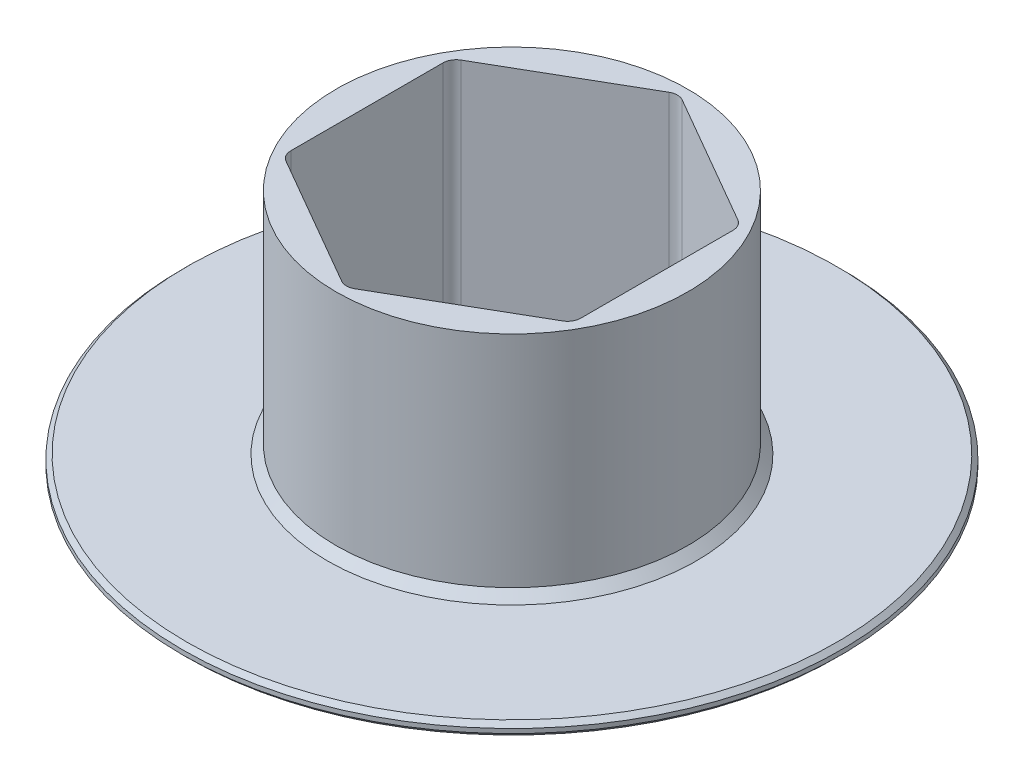
SolidWorks part; units mm, degrees
ref_plane "Front Plane" through (0, 0, 0) normal (0, 0, 1) x (1, 0, 0)
ref_plane "Top Plane" through (0, 0, 0) normal (0, 1, 0) x (1, 0, 0)
ref_plane "Right Plane" through (0, 0, 0) normal (1, 0, 0) x (0, 0, -1)
sketch "Sketch1" plane through (0, 0, 0) normal (0, 1, 0) x (1, 0, 0)
  line L1 (33, -19.0526) -> (33, 19.0526)
  line L2 (33, 19.0526) -> (0, 38.1051)
  line L3 (0, 38.1051) -> (-33, 19.0526)
  line L4 (-33, 19.0526) -> (-33, -19.0526)
  line L5 (-33, -19.0526) -> (0, -38.1051)
  line L6 (0, -38.1051) -> (33, -19.0526)
  circle A0 centre (0, 0) radius 75
  circle A1 centre (0, 0) radius 40
  circle A2 centre (0, 0) radius 33 construction
  dimension "D2" = 80
  dimension "D3" = 150
  dimension "D1" = 66
extrude "Boss-Extrude1" add sketch "Sketch1" along normal blind 3 contours A0 A1 | A1 L6 L5 L4 L3 L2 L1 | L5 L6 L1 L2 L3 L4 region at (0, 0, 0) region at (-72.8787, 0, 0) region at (-38.8686, 0, 0)
extrude "Boss-Extrude2" add sketch "Sketch1<3>" along normal blind 55 contours A1 L6 L5 L4 L3 L2 L1 region at (-38.8686, 0, 0)
sketch "Sketch1<3>" plane through (0, 0, 0) normal (0, 1, 0) x (1, 0, 0) same geometry as "Sketch1"
sketch "Sketch2" plane through (0, 3, 0) normal (0, 1, 0) x (1, 0, 0)
  circle A0 centre (0, 0) radius 26
  dimension "D1" = 52
extrude "Cut-Extrude1" cut sketch "Sketch2" against normal through all
fillet "Fillet1" radius 3 6 edges at (33, 29, 19.0526) (0, 29, 38.1051) (-33, 29, 19.0526) (-33, 29, -19.0526) (0, 29, -38.1051) (33, 29, -19.0526)
chamfer "Chamfer2" distance 2 angle 45 12 edges at (-16.5, 3, -28.5788) (0, 3, -37.641) (-32.5981, 3, -18.8205) (16.5, 3, -28.5788) (-33, 3, 0) (32.5981, 3, -18.8205) (-32.5981, 3, 18.8205) (33, 3, 0) (-16.5, 3, 28.5788) (32.5981, 3, 18.8205) (0, 3, 37.641) (16.5, 3, 28.5788)
chamfer "Chamfer3" distance 2 angle 45 1 edges at (0, 3, 40)
chamfer "Chamfer4" distance 1 angle 45 2 edges at (0, 3, 75) (0, 0, 75)
sketch "Sketch3" plane through (0, 0, 0) normal (0, -1, 0) x (1, 0, 0)
  line L1 (32.5, -18.7639) -> (32.5, 18.7639)
  line L2 (32.5, 18.7639) -> (0, 37.5278)
  line L3 (0, 37.5278) -> (-32.5, 18.7639)
  line L4 (-32.5, 18.7639) -> (-32.5, -18.7639)
  line L5 (-32.5, -18.7639) -> (0, -37.5278)
  line L6 (0, -37.5278) -> (32.5, -18.7639)
  circle A0 centre (0, 0) radius 32.5 construction
  circle A1 centre (0, 0) radius 26 construction
  circle A2 centre (0, 0) radius 26
  dimension "D1" = 65
extrude "Boss-Extrude3" add sketch "Sketch3" along normal blind 17
fillet "Fillet3" radius 3 6 edges at (32.5, -8.5, -18.7639) (32.5, -8.5, 18.7639) (0, -8.5, 37.5278) (-32.5, -8.5, 18.7639) (-32.5, -8.5, -18.7639) (0, -8.5, -37.5278)
